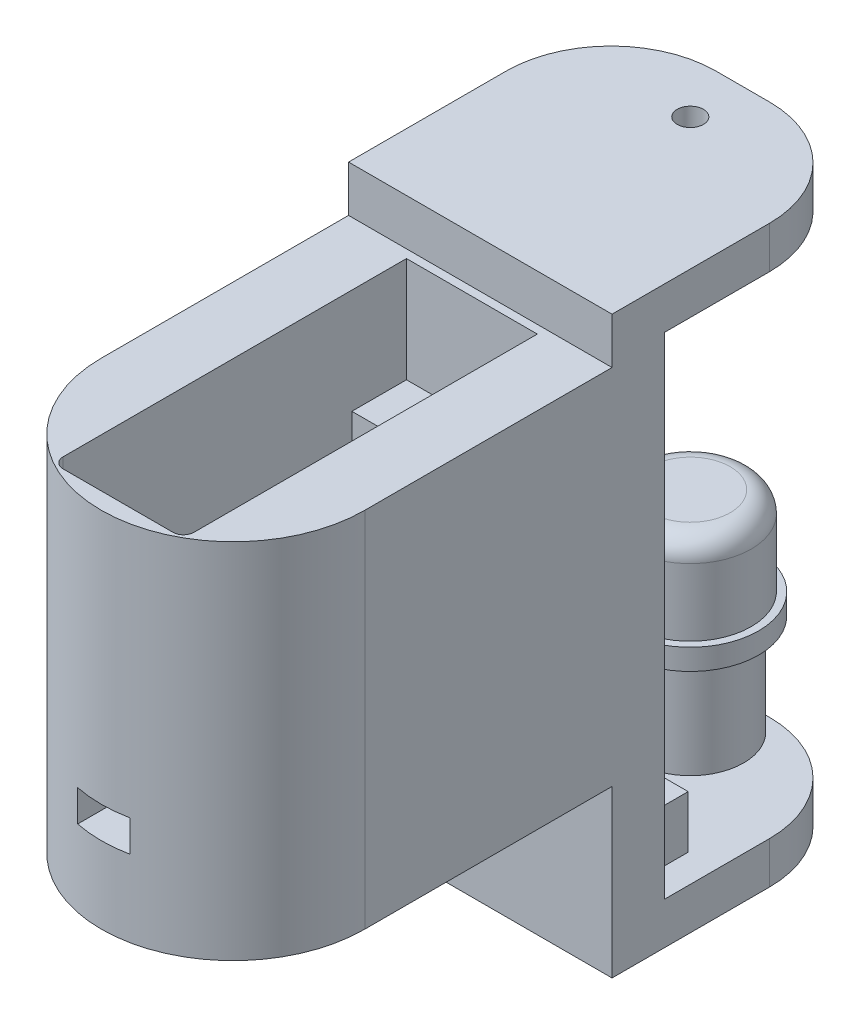
SolidWorks part; units mm, degrees
ref_plane "Front Plane" through (0, 0, 0) normal (0, 0, 1) x (1, 0, 0)
ref_plane "Top Plane" through (0, 0, 0) normal (0, 1, 0) x (1, 0, 0)
ref_plane "Right Plane" through (0, 0, 0) normal (1, 0, 0) x (0, 0, -1)
sketch "Sketch4" plane through (0, 0, 0) normal (0, 0, 1) x (1, 0, 0)
  line L1 (-6.23, -9.975) -> (6.23, -9.975)
  line L2 (-6.23, -9.975) -> (-6.23, 7.275)
  line L3 (-6.23, 7.275) -> (6.23, 7.275)
  line L4 (6.23, -9.975) -> (6.23, 7.275)
  point P4 (0, 7.275)
  dimension "D1" = 12.46
  dimension "D2" = 17.25
  dimension "D3" = 9.975
extrude "Boss-Extrude3" add sketch "Sketch4" along normal blind 6
sketch "Sketch8" plane through (0, -9.975, 0) normal (0, -1, 0) x (-1, 0, 0)
  circle A0 centre (0, -23.55) radius 12.5468
  circle A1 centre (0, -23.55) radius 11.15
  dimension "D1" = 22.3
  dimension "D2" = 23.55
extrude "Boss-Extrude6" add sketch "Sketch8" along normal blind 7.3 and the other way up to surface (17.25 mm away) other way up to face at (0, 7.275, 3)
sketch "Sketch5" plane through (0, 7.275, 0) normal (0, 1, 0) x (1, 0, 0)
  line L8 (12.5468, -23.55) -> (12.5468, 0)
  line L9 (12.5468, 0) -> (6.23, 0)
  line L10 (-12.5468, -23.55) -> (-12.5468, 0)
  line L11 (-12.5468, 0) -> (-6.23, 0)
  line L12 (-6.23, 0) -> (-6.23, -29.7)
  line L14 (6.23, -29.7) -> (6.23, 0)
  line L15 (-6.23, -29.7) -> (6.23, -29.7)
  line L16 (6.23, -6) -> (-6.23, -6) construction
  circle A0 centre (0, -23.55) radius 12.5468 construction
  arc A1 (-12.5468, -23.55) -> (12.5468, -23.55) centre (0, -23.55) ccw
  dimension "D1" = 23.7
  dimension "D2" = 23.55
extrude "Boss-Extrude4" add sketch "Sketch5" against normal up to surface (17.25 mm away) up to face at (0, -9.975, 3)
sketch "Sketch6" plane through (0, 7.275, 0) normal (0, 1, 0) x (1, 0, 0)
  line L0 (6.23, -6) -> (-6.23, -6) construction
  line L3 (6.23, -29.7) -> (-6.23, -29.7) construction
  circle A0 centre (0, -3.6) radius 0.5
  circle A1 centre (0, -32.1) radius 0.5
  dimension "D1" = 1
  dimension "D3" = 1
  dimension "D2" = 2.4
  dimension "D4" = 2.4
extrude "Cut-Extrude1" cut sketch "Sketch6" against normal blind 15
chamfer "Chamfer1" distance 0.5 angle 60 2 edges at (0, 7.275, 4.1) (0, 7.275, 32.6) first distance on face at (0, 7.275, 4.1)
sketch "Sketch10" plane through (0, 7.275, 0) normal (0, 1, 0) x (1, 0, 0)
  line L1 (-6.23, -6) -> (6.23, -6)
  line L2 (-6.23, -6) -> (-6.23, -29.7)
  line L3 (-6.23, -29.7) -> (6.23, -29.7)
  line L4 (6.23, -6) -> (6.23, -29.7)
extrude "Cut-Extrude3" cut sketch "Sketch10" against normal up to surface (17.25 mm away) up to face at (0, -9.975, 27.1007)
ref_plane "Plane1" through (0, 0, 36.0968) normal (0, 0, 1) x (1, 0, 0)
sketch "Sketch11" plane through (0, 0, 36.0968) normal (0, 0, 1) x (1, 0, 0)
  line L0 (-11.15, -9.975) -> (11.15, -9.975) construction
  line L1 (-2.5, -6.975) -> (2.5, -6.975)
  line L2 (-2.5, -6.975) -> (-2.5, -9.975)
  line L3 (-2.5, -9.975) -> (2.5, -9.975)
  line L4 (2.5, -6.975) -> (2.5, -9.975)
  point P4 (0, -6.975)
  dimension "D1" = 0
  dimension "D2" = 5
  dimension "D3" = 3
extrude "Cut-Extrude4" cut sketch "Sketch11" against normal up to next
sketch "Sketch13" plane through (0, -17.275, 0) normal (0, -1, 0) x (1, 0, 0)
  line L0 (-12.5468, 23.55) -> (-12.5468, 0)
  line L1 (-12.5468, 0) -> (12.5468, 0)
  line L2 (12.5468, 0) -> (12.5468, 23.55)
  arc A0 (-12.5468, 23.55) -> (12.5468, 23.55) centre (0, 23.55) ccw
  point P3 (0, 0)
extrude "Boss-Extrude7" add sketch "Sketch13" against normal up to surface (7.3 mm away) up to face at (6.0145, -9.975, 27.3356)
sketch "Sketch15" plane through (0, 7.275, 0) normal (0, 1, 0) x (1, 0, 0)
  line L0 (-12.5468, 0) -> (12.5468, 0)
  line L1 (12.5468, 0) -> (12.5468, -23.55)
  line L2 (-12.5468, 0) -> (-12.5468, -23.55)
  line L3 (6.23, -6) -> (6.23, -29.7) construction
  line L4 (-6.23, -0.8) -> (6.23, -0.8)
  line L5 (-6.23, -0.8) -> (-6.23, -33.5)
  line L6 (-5.23, -34.5) -> (5.23, -34.5)
  line L7 (6.23, -0.8) -> (6.23, -33.5)
  arc A0 (-12.5468, -23.55) -> (12.5468, -23.55) centre (0, -23.55) ccw
  circle A1 centre (0, -3.6) radius 0.5 construction
  arc A2 (5.23, -34.5) -> (6.23, -33.5) centre (5.23, -33.5) ccw
  arc A3 (-6.23, -33.5) -> (-5.23, -34.5) centre (-5.23, -33.5) ccw
  point P15 (0, -0.8)
  dimension "D1" = 0.8
  dimension "D3" = 1
  dimension "D2" = 2.8
  dimension "D4" = 0
  dimension "D5" = 34.5
extrude "Boss-Extrude9" add sketch "Sketch15" along normal blind 10
sketch "Sketch20" plane through (0, -17.275, 0) normal (0, -1, 0) x (1, 0, 0)
  circle A0 centre (0, 23.55) radius 7.15
  circle A1 centre (0, 23.55) radius 11.15
  circle A2 centre (0, 23.55) radius 11.15 construction
  dimension "D1" = 14.3
extrude "Boss-Extrude11" add sketch "Sketch20" against normal up to surface (7.3 mm away) up to face at (-6.0145, -9.975, 27.3356)
sketch "Sketch21" plane through (0, -17.275, 0) normal (0, -1, 0) x (1, 0, 0)
  circle A0 centre (0, 23.55) radius 7.15
  circle A1 centre (0, 23.55) radius 10.15
  circle A2 centre (0, 23.55) radius 7.15 construction
  dimension "D1" = 20.3
extrude "Cut-Extrude7" cut sketch "Sketch21" against normal blind 1.3
sketch "Sketch17" plane through (12.5468, 4.7282, 0) normal (-1, 0, 0) x (0, 1, 0)
  line L0 (16.9468, 25) -> (16.9468, 0)
  line L1 (16.9468, 0) -> (-37.8032, 0)
  line L2 (-37.8032, 0) -> (-37.8032, 25)
  line L3 (-37.8032, 25) -> (-33.8032, 25)
  line L4 (-33.8032, 25) -> (-33.8032, 5)
  line L5 (-33.8032, 5) -> (12.9468, 5)
  line L6 (12.9468, 5) -> (12.9468, 25)
  line L7 (12.9468, 25) -> (16.9468, 25)
  line L8 (-22.0032, -23.55) -> (-22.0032, 0) construction
  line L10 (12.5468, 0) -> (12.5468, -23.55) construction
  dimension "D1" = 4
  dimension "D2" = 0.4
  dimension "D3" = 4
  dimension "D4" = 25
  dimension "D5" = 5
  dimension "D6" = 15.8
extrude "Boss-Extrude10" add sketch "Sketch17" along normal up to surface (25.0936 mm away) up to face at (-12.5468, 0, 11.775)
sketch "Sketch18" plane through (0, 17.675, 0) normal (0, -1, 0) x (0, 0, 1)
  line L0 (-25, -12.5468) -> (-25, 12.5468) construction
  line L1 (-25, 6.2191) -> (-5, 6.2191)
  line L2 (-25, 6.2191) -> (-25, -6.2191)
  line L3 (-25, -6.2191) -> (-5, -6.2191)
  line L4 (-5, 6.2191) -> (-5, -6.2191)
  line L5 (-5, -12.5468) -> (-5, 12.5468) construction
  point P6 (-25, 0)
  point P7 (-25, 0)
  dimension "D1" = 0
extrude "Cut-Extrude5" cut sketch "Sketch18" against normal blind 2
sketch "Sketch19" plane through (0, 19.675, 0) normal (0, -1, 0) x (0, 0, 1)
  line L0 (-25, -12.5468) -> (-25, 12.5468) construction
  circle A0 centre (-20, 0) radius 1.25
  dimension "D1" = 2.5
  dimension "D2" = 5
extrude "Cut-Extrude6" cut sketch "Sketch19" against normal through all both and the other way through all
fillet "Fillet1" radius 10 4 edges at (-12.5468, 19.675, -25) (12.5468, 19.675, -25) (12.5468, -31.075, -25) (-12.5468, -31.075, -25)
ref_plane "Plane2" through (0, 0, 0) normal (1, 0, 0) x (0, 0, -1)
ref_plane "Plane3" through (0, 0, 0) normal (0, -1, 0) x (-1, 0, 0)
sketch "Sketch22" plane through (0, -29.075, 0) normal (0, 1, 0) x (0, 0, -1)
  circle A0 centre (20, 0) radius 5.8
  dimension "D1" = 11.6
extrude "Boss-Extrude12" add sketch "Sketch22" along normal blind 20
fillet "Fillet2" radius 2 1 edges at (-5.8, -9.075, -20)
sketch "Sketch23" plane through (0, -29.075, 0) normal (0, 1, 0) x (0, 0, -1)
  circle A0 centre (20, 0) radius 5.08
  circle A1 centre (20, 0) radius 5.9309
  dimension "D1" = 10.16
extrude "Cut-Extrude8" cut sketch "Sketch23" along normal blind 11.6
sketch "Sketch24" plane through (0, -17.475, 0) normal (0, -1, 0) x (0, 0, 1)
  circle A0 centre (-20, 0) radius 6.5
extrude "Boss-Extrude13" add sketch "Sketch24" along normal blind 2
sketch "Sketch25" plane through (0, -33.075, 0) normal (0, -1, 0) x (0, 0, 1)
  circle A0 centre (-20, 0) radius 1.25
extrude "Boss-Extrude14" add sketch "Sketch25" against normal blind 2
sketch "Sketch26" plane through (0, -29.075, 0) normal (0, 1, 0) x (0, 0, -1)
  line L0 (5, -12.5468) -> (5, 12.5468) construction
  line L1 (5, -9.7968) -> (10, -9.7968)
  line L2 (5, -9.7968) -> (5, -6.7968)
  line L3 (5, -6.7968) -> (10, -6.7968)
  line L4 (10, -9.7968) -> (10, -6.7968)
  line L6 (5, -5.2808) -> (10, -5.2808)
  line L7 (5, -5.2808) -> (5, -2.2808)
  line L8 (5, -2.2808) -> (10, -2.2808)
  line L9 (10, -5.2808) -> (10, -2.2808)
  line L10 (5, -12.5468) -> (15, -12.5468) construction
  dimension "D1" = 1.516
  dimension "D2" = 3
  dimension "D3" = 3
  dimension "D4" = 0
  dimension "D5" = 5
  dimension "D6" = 2.75
extrude "Boss-Extrude15" add sketch "Sketch26" along normal blind 5
